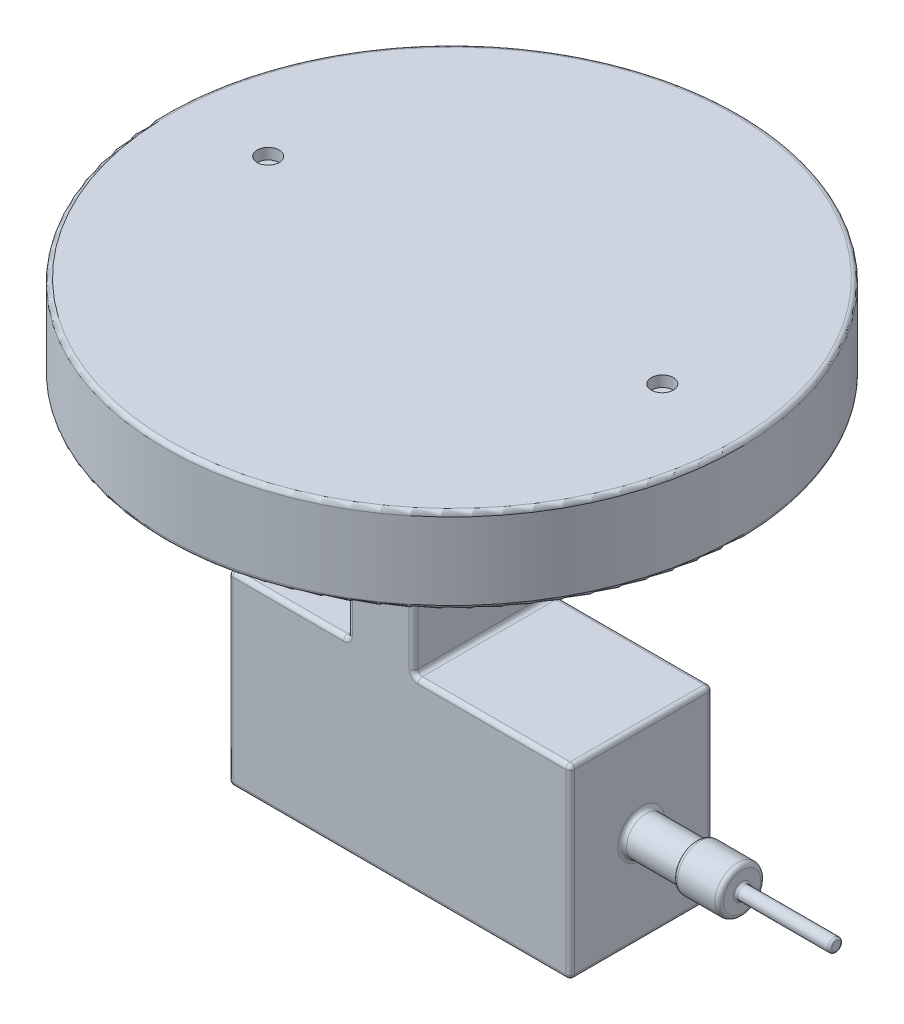
SolidWorks part; units mm, degrees
ref_plane "Front Plane" through (0, 0, 0) normal (0, 0, 1) x (1, 0, 0)
ref_plane "Top Plane" through (0, 0, 0) normal (0, 1, 0) x (1, 0, 0)
ref_plane "Right Plane" through (0, 0, 0) normal (1, 0, 0) x (0, 0, -1)
sketch "Sketch1" plane through (0, 0, 0) normal (0, 1, 0) x (1, 0, 0)
  line L1 (0, 0) -> (156, 0)
  line L2 (0, 0) -> (0, 65)
  line L3 (0, 65) -> (156, 65)
  line L4 (156, 0) -> (156, 65)
  dimension "D1" = 156
  dimension "D2" = 65
extrude "Boss-Extrude1" add sketch "Sketch1" along normal blind 85
sketch "Sketch2" plane through (156, 0, 0) normal (1, 0, 0) x (0, 0, -1)
  line L0 (0, 85) -> (0, 0) construction
  line L1 (0, 0) -> (65, 0) construction
  circle A0 centre (32.5, 42.5) radius 10.5
  point P2 (0, 42.5)
  dimension "D1" = 21
  dimension "D3" = 42.5
  dimension "D2" = 32.5
extrude "Boss-Extrude2" add sketch "Sketch2" along normal blind 46
sketch "Sketch3" plane through (202, 0, 0) normal (1, 0, 0) x (0, 0, -1)
  circle A0 centre (32.5, 42.5) radius 3
  dimension "D1" = 6
extrude "Boss-Extrude3" add sketch "Sketch3" along normal blind 43
sketch "Sketch4" plane through (156, 0, 0) normal (1, 0, 0) x (0, 0, -1)
  circle A0 centre (32.5, 42.5) radius 8.75
  circle A1 centre (32.5, 42.5) radius 10.5
  dimension "D1" = 17.5
extrude "Cut-Extrude2" cut sketch "Sketch4" along normal blind 25
sketch "Sketch5" plane through (0, 85, 0) normal (0, 1, 0) x (1, 0, 0)
  line L0 (156, 65) -> (0, 65) construction
  line L1 (54.5, 65) -> (84.5, 65)
  line L2 (54.5, 65) -> (54.5, 0)
  line L3 (54.5, 0) -> (84.5, 0)
  line L4 (84.5, 65) -> (84.5, 0)
  line L5 (0, 0) -> (156, 0) construction
  line L6 (0, 65) -> (0, 0) construction
  dimension "D1" = 30
  dimension "D2" = 54.5
extrude "Boss-Extrude4" add sketch "Sketch5" along normal blind 95
sketch "Sketch6" plane through (0, 180, 0) normal (0, 1, 0) x (1, 0, 0)
  circle A0 centre (69.5, 32.5) radius 131
  dimension "D1" = 262
extrude "Boss-Extrude5" add sketch "Sketch6" along normal blind 39
sketch "Sketch7" plane through (0, 219, 0) normal (0, 1, 0) x (-1, 0, 0)
  circle A0 centre (20.5, -38.588) radius 5
  circle A1 centre (-69.5, -32.5) radius 131 construction
  circle A2 centre (-159.5, -38.588) radius 5
  dimension "D1" = 10
  dimension "D2" = 90
  dimension "D3" = 90
extrude "Cut-Extrude3" cut sketch "Sketch7" against normal blind 5
fillet "Fillet10" radius 2 1 edges at (0, 42.5, 0)
fillet "Fillet11" radius 2 12 edges at (79, 0, 0) (0, 0, -33.5) (0, 85, -33.5) (0, 42.5, -65) (0.5858, 0, -0.5858) (0.5858, 85, -0.5858)
fillet "Fillet12" radius 2 11 edges at (79, 0, -65) (156, 0, -33.5) (0.5858, 0.5858, -64.4142) (156, 43.5, 0) (156, 0.5858, -0.5858) (85.0858, 85.5858, -65) (85.0858, 85.5858, 0)
fillet "Fillet13" radius 2 10 edges at (155.4142, 84.4142, -0.5858) (156, 85, -32.5) (156, 84.4142, -64.4142) (155.4142, 0.5858, -64.4142) (156, 42.5, -41.25) (181, 42.5, -43) (202, 42.5, -43) (69.5, 180, 98.5) (69.5, 219, 98.5) (156, 42.5, -65)
fillet "Fillet14" radius 1 1 edges at (245, 42.5, -35.5)
fillet "Fillet15" radius 1 1 edges at (202, 42.5, -35.5)
